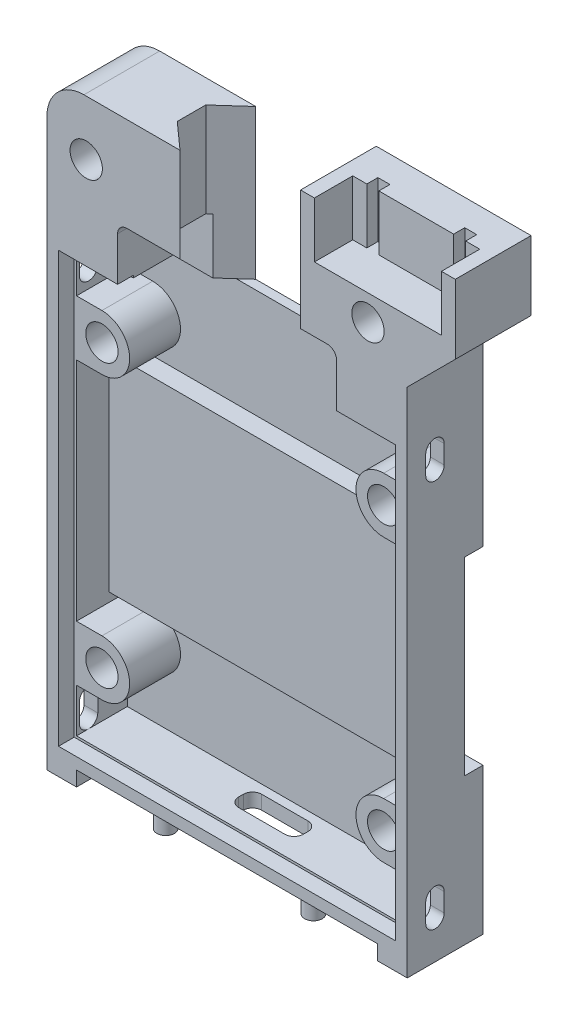
SolidWorks part; units mm, degrees
ref_plane "Front Plane" through (0, 0, 0) normal (0, 0, 1) x (1, 0, 0)
ref_plane "Top Plane" through (0, 0, 0) normal (0, 1, 0) x (1, 0, 0)
ref_plane "Right Plane" through (0, 0, 0) normal (1, 0, 0) x (0, 0, -1)
sketch "Sketch1" plane through (0, 0, 0) normal (0, 0, 1) x (1, 0, 0)
  line L0 (15.25, -20.35) -> (18, -20.35)
  line L1 (-19.5, -32.6) -> (19.5, -32.6)
  line L2 (-19.5, -32.6) -> (-19.5, 31.1)
  line L3 (-19.5, 31.1) -> (19.5, 31.1)
  line L4 (19.5, -32.6) -> (19.5, 31.1)
  line L5 (-15.25, -20.35) -> (-18, -20.35)
  line L6 (15.25, -26.35) -> (18, -26.35)
  line L7 (6.95, 31.1) -> (-15.5, 31.1) construction
  line L8 (-18, -31.1) -> (-18, 29.6)
  line L9 (-18, 29.6) -> (18, 29.6)
  line L10 (18, -31.1) -> (18, 29.6)
  line L11 (-18, -31.1) -> (18, -31.1)
  line L12 (-18, 14.9) -> (18, 14.9)
  line L13 (7.85, 14.9) -> (-4.95, 14.9) construction
  line L14 (-15.25, 4.15) -> (-18, 4.15)
  line L15 (-15.25, 10.15) -> (-18, 10.15)
  line L16 (15.25, 10.15) -> (18, 10.15)
  line L17 (15.25, 4.15) -> (18, 4.15)
  line L18 (-15.25, -26.35) -> (-18, -26.35)
  line L19 (19.5, -34.2) -> (19.5, -18.35) construction
  line L20 (-19.5, -34.2) -> (-19.5, -18.35) construction
  line L21 (15.3, -32.6) -> (-15.3, -32.6) construction
  line L22 (0, 31.1) -> (0, -32.6) construction
  line L23 (9.45, 26.9) -> (24.7, 26.9)
  line L24 (9.45, 26.9) -> (9.45, 33.9)
  line L25 (9.45, 33.9) -> (24.7, 33.9)
  line L26 (24.7, 26.9) -> (24.7, 33.9)
  line L27 (18, 29.6) -> (19.5, 31.1) construction
  line L28 (18.75, 30.35) -> (0, 30.35) construction
  line L29 (9.45, 26.9) -> (7.95, 26.9) construction
  line L30 (-7.95, 31.1) -> (7.95, 31.1)
  line L31 (-7.95, 31.1) -> (-7.95, 29.6)
  line L32 (-7.95, 29.6) -> (7.95, 29.6)
  line L33 (7.95, 31.1) -> (7.95, 29.6)
  line L34 (-7.95, 31.1) -> (7.95, 29.6) construction
  line L35 (-7.95, 29.6) -> (7.95, 31.1) construction
  line L36 (7.95, 26.9) -> (7.95, 29.6) construction
  line L37 (18, 29.6) -> (19.5, 29.6) construction
  line L38 (24.7, 26.4) -> (19.5, 21.2)
  line L39 (9.45, 33.9) -> (7.95, 33.9)
  line L40 (23.2, 33.9) -> (23.2, 26.9)
  line L41 (7.95, 33.9) -> (7.95, 31.1)
  line L42 (24.7, 30.4) -> (23.2, 30.4) construction
  line L43 (24.7, 26.9) -> (19.5, 26.9)
  line L44 (24.7, 26.9) -> (24.7, 26.4)
  line L45 (24.7, 26.4) -> (19.5, 26.4)
  line L46 (19.5, 26.9) -> (19.5, 26.4)
  circle A0 centre (15.25, -23.35) radius 1.75
  arc A1 (-15.5, 31.1) -> (-19.5, 27.1) centre (-15.5, 27.1) ccw construction
  circle A2 centre (15.25, -23.35) radius 3
  arc A3 (-15.5, 31.1) -> (-19.5, 27.1) centre (-15.5, 27.1) ccw
  arc A4 (-15.5, 29.6) -> (-18, 27.1) centre (-15.5, 27.1) ccw
  circle A6 centre (-15.25, -23.35) radius 1.75
  circle A7 centre (-15.25, -23.35) radius 1.75
  circle A8 centre (-15.25, 7.15) radius 1.75
  circle A9 centre (15.25, 7.15) radius 1.75
  circle A10 centre (15.25, 25.15) radius 1.75
  circle A11 centre (-15.25, 25.15) radius 1.75
  circle A12 centre (-15.25, -23.35) radius 3
  circle A13 centre (-15.25, -23.35) radius 3
  circle A14 centre (15.25, 7.15) radius 3
  circle A15 centre (-15.25, 7.15) radius 3
  dimension "D2" = 1.5
  dimension "D4" = 6
  dimension "D3" = 3.5
  dimension "D5" = 13.75
  dimension "D6" = 15.9
  dimension "D7" = 7
  dimension "D8" = 45
  dimension "D9" = 0.5
  dimension "D1" = 1.5
extrude "Base shape" add sketch "Sketch1" along normal up to surface (8.2 mm away) contours A15 L8 L9 L31 L3 A3 L2 L1 L4 L23 L10 A14 A2 L11 A12 | A12 L8 L18 | A12 L8 A6 | L8 A12 | A12 L5 L8 | A15 L8 L14 | A15 L8 A8 | L8 A15 | A15 L15 L8 | L23 A10 L24 L9 A4 L8 L12 L10 A11 | A4 L9 L8 | L33 L3 L31 L9 | L3 L33 L9 L24 | L24 L9 L10 L23 L4 L3 | L24 L23 L10 L9 | A14 L10 L16 | L10 A14 A9 | A14 L17 L10 | L10 A14 | L10 A2 L6 | A2 L10 A0 | L0 A2 L10 | A2 L10 | L40 L25 L24 L3 L4 L23 | L25 L40 L23 L26 | L38 L45 L4 | L45 L44 L23 L4 | L39 L41 L3 L24 region at (16.8481, -20.9099, 0) region at (17.3601, -20.8437, 0) region at (18.7469, -8.1, 0) region at (17.3601, -25.8563, 0) region at (18.1004, -23.35, 0) region at (17.3601, 4.6437, 0) region at (16.8481, 4.7099, 0) region at (18.1004, 7.15, 0) region at (17.3601, 9.6563, 0) region at (-17.3601, -25.8563, 0) region at (-0.6044, 21.831, 0) region at (-18.1004, -23.35, 0) region at (-17.9169, -23.35, 0) region at (13.725, 28.25, 0) region at (15.3803, 29.9053, 0) region at (-17.3601, -20.8437, 0) region at (22.1, 26.65, 0) region at (17.77, 31.4935, 0) region at (-17.3601, 9.6563, 0) region at (-17.4416, 29.0416, 0) region at (8.7, 30.35, 0) region at (21.2333, 24.6667, 0) region at (23.95, 30.4, 0) region at (-16.8481, 9.5901, 0) region at (-18.1004, 7.15, 0) region at (-17.3601, 4.6437, 0) region at (0, 30.35, 0) region at (8.7, 32.5, 0)
sketch "Sketch3" plane through (19.5, 0, 0) normal (1, 0, 0) x (0, 0, -1)
  line L1 (0, -18.35) -> (-2, -18.35)
  line L2 (0, -18.35) -> (0, 2.15)
  line L3 (0, 2.15) -> (-2, 2.15)
  line L4 (-2, -18.35) -> (-2, 2.15)
  line L5 (0, -18.35) -> (1.75, -18.35) construction
  line L6 (0, 2.15) -> (1.75, 2.15) construction
  line L7 (0, -32.6) -> (0, 21.2) construction
  dimension "D1" = 2
extrude "Strap cut" cut sketch "Sketch3" against normal through all
sketch "Sketch4" plane through (0, 31.1, 0) normal (0, 1, 0) x (1, 0, 0)
  line L2 (7.95, 0) -> (-5.0998, 0)
  line L4 (-15.5, 0) -> (7.95, 0) construction
  line L5 (-15.5, -8.2) -> (7.95, -8.2) construction
  line L6 (7.95, -8.2) -> (-5.0998, -8.2)
  line L12 (7.95, -8.3) -> (7.95, 0.1)
  line L13 (7.95, 0.1) -> (-4.9883, 0.1)
  line L14 (-4.9883, 0.1) -> (-7.95, -2.5553)
  line L15 (-7.95, -2.5553) -> (-7.95, -5.6447)
  line L16 (-7.95, -5.6447) -> (-4.9883, -8.3)
  line L17 (-4.9883, -8.3) -> (7.95, -8.3)
  line L18 (7.95, -8.3) -> (7.95, 0.1)
  line L19 (7.95, 0.1) -> (-4.9883, 0.1)
  line L20 (-4.9883, 0.1) -> (-7.95, -2.5553)
  line L21 (-7.95, -2.5553) -> (-7.95, -5.6447)
  line L22 (-7.95, -5.6447) -> (-4.9883, -8.3)
  line L23 (-4.9883, -8.3) -> (7.95, -8.3)
  dimension "D1" = 0.1
extrude "XT60 cut" cut sketch "Sketch4" against normal up to next contours L21 L22 L18 L20 region at (0.4142, 31.1, 4.1)
sketch "Sketch5" plane through (19.5, 0, 0) normal (1, 0, 0) x (0, 0, -1)
  line L1 (-8.2, -32.6) -> (-8.2, 21.2) construction
  line L2 (-6.2, -31.1) -> (-4.2, -31.1)
  line L3 (-6.2, -31.1) -> (-6.2, -27.1)
  line L4 (-6.2, -27.1) -> (-4.2, -27.1)
  line L5 (-4.2, -31.1) -> (-4.2, -27.1)
  line L6 (-8.2, -31.1) -> (0, -31.1) construction
  line L7 (-8.2, 14.9) -> (0, 14.9) construction
  line L8 (-6.2, 14.9) -> (-4.2, 14.9)
  line L9 (-6.2, 14.9) -> (-6.2, 10.9)
  line L10 (-6.2, 10.9) -> (-4.2, 10.9)
  line L11 (-4.2, 14.9) -> (-4.2, 10.9)
  line L14 (-5.2, -27.1) -> (-5.2, -31.1) construction
  line L15 (-5.2, 14.9) -> (-5.2, 10.9) construction
  circle A0 centre (-5.2, -28.1) radius 1
  circle A1 centre (-5.2, -30.1) radius 1
  circle A2 centre (-5.2, 13.9) radius 1
  circle A3 centre (-5.2, 11.9) radius 1
  point P20 (-5.2, -29.1)
  point P31 (-5.2, 12.9)
  dimension "D3" = 4
  dimension "D1" = 2
  dimension "D2" = 2
extrude "Power wires cut" cut sketch "Sketch5" against normal through all contours A2 | A3 | A3 A2 L9 | A3 L11 A2 | A1 | A0 | A1 L5 A0 | A1 A0 L3 region at (19.5, -30.1, 5.2) region at (19.5, -29.1, 5.9766) region at (19.5, -29.1, 4.4234) region at (19.5, -28.1, 5.2) region at (19.5, 13.9, 5.2) region at (19.5, 12.9, 5.9766) region at (19.5, 12.9, 4.4234) region at (19.5, 11.9, 5.2)
sketch "Sketch6" plane through (0, 0, 8.2) normal (0, 0, 1) x (1, 0, 0)
  line L5 (-10.85, 20.9) -> (10.85, 20.9)
  line L6 (10.85, 14.9) -> (8.85, 14.9) construction
  line L7 (-11.85, 19.9) -> (11.85, 19.9)
  line L12 (-11.85, 19.9) -> (-11.85, 14.9)
  line L14 (-11.85, 14.9) -> (11.85, 14.9)
  line L15 (11.85, 19.9) -> (11.85, 14.9)
  arc A7 (11.85, 19.9) -> (10.85, 20.9) centre (10.85, 19.9) ccw construction
  arc A12 (11.85, 19.9) -> (10.85, 20.9) centre (10.85, 19.9) ccw
  arc A13 (-10.85, 20.9) -> (-11.85, 19.9) centre (-10.85, 19.9) ccw construction
  arc A14 (-10.85, 20.9) -> (-11.85, 19.9) centre (-10.85, 19.9) ccw
  point P9 (0, 0)
extrude "IO wires cut" cut sketch "Sketch6" against normal blind 6
sketch "Sketch7" plane through (-18, 0, 0) normal (1, 0, 0) x (0, 0, -1)
  line L6 (0, -18.35) -> (0, -20.35)
  line L7 (-2, -18.35) -> (0, -18.35)
  line L8 (-2, 2.15) -> (-2, -18.35)
  line L9 (0, 2.15) -> (-2, 2.15)
  line L12 (0, 3.15) -> (-3, 3.15)
  line L13 (-3, 3.15) -> (-3, -19.35)
  line L14 (-3, -19.35) -> (-1, -19.35)
  line L15 (-1, -19.35) -> (-1, -20.35)
  line L16 (-1, -20.35) -> (0, -20.35)
  line L17 (0, 3.15) -> (-1, 3.15)
  line L19 (0, -31.1) -> (-1, -31.1)
  line L22 (0, -31.1) -> (0, -20.35)
  line L23 (0, -20.35) -> (-1, -20.35)
  line L24 (-1, -31.1) -> (-1, -20.35)
  line L25 (0, 3.15) -> (0, 14.9)
  line L26 (0, 14.9) -> (-1, 14.9)
  line L27 (-1, 3.15) -> (-1, 14.9)
  line L28 (-5.2, 14.9) -> (0, 14.9) construction
  line L31 (0, -20.35) -> (0, -18.35) construction
  line L32 (0, 2.15) -> (-2, 2.15) construction
  line M48 (0, -20.35) -> (0, -18.35)
  line M49 (0, -18.35) -> (-2, -18.35)
  line M50 (-2, -18.35) -> (-2, 2.15)
  line M51 (-2, 2.15) -> (0, 2.15)
  line M52 (0, 2.15) -> (0, 4.15)
  line M53 (0, 4.15) -> (-8.2, 4.15)
  line M55 (-8.2, -20.35) -> (0, -20.35)
  dimension "D1" = 1
extrude "Bottom" add sketch "Sketch7" along normal up to surface (36 mm away) contours L27 L25 L26 M53 | L27 L12 M52 M53 | L14 L15 L12 L13 M55 M48 M49 M50 M51 M52 | L24 L19 L22 M55 region at (-18, -8.5273, 2.2091) region at (-18, -25.725, 0.5) region at (-18, 3.65, 0.5) region at (-18, 9.525, 0.5) up to face at (18, -8.1, 2.55)
sketch "Sketch9" plane through (0, 0, 0) normal (0, 0, -1) x (-1, 0, 0)
  circle A0 centre (15.25, -23.35) radius 1.75 construction
  circle A1 centre (-15.25, 7.15) radius 1.75 construction
  circle A2 centre (15.25, 7.15) radius 1.75 construction
  circle A3 centre (15.25, -23.35) radius 1.75 construction
  circle A4 centre (15.25, -23.35) radius 1.75
  circle A5 centre (-15.25, 7.15) radius 1.75
  circle A6 centre (15.25, 7.15) radius 1.75
  circle A7 centre (15.25, -23.35) radius 1.75
  circle A8 centre (-15.25, -23.35) radius 1.75 construction
  circle A9 centre (-15.25, -23.35) radius 1.75
extrude "Bottom holes" cut sketch "Sketch9" against normal up to next contours A5 | A6 | A4 | A9 region at (-15.25, -23.35, 0) region at (15.25, 7.15, 0) region at (-15.25, 7.15, 0) region at (15.25, -23.35, 0)
sketch "Sketch8" plane through (0, 0, 8.2) normal (0, 0, 1) x (1, 0, 0)
  line L0 (-6.2152, 14.9) -> (-18, 14.9) construction
  line L1 (-18.25, 15.15) -> (18.25, 15.15)
  line L2 (-18.25, 15.15) -> (-18.25, -31.35)
  line L3 (-18.25, -31.35) -> (18.25, -31.35)
  line L4 (18.25, 15.15) -> (18.25, -31.35)
  line L5 (-18, 14.9) -> (-18.25, 14.9) construction
  line L6 (-18, 14.9) -> (-18, 15.15) construction
  line L7 (18, 14.9) -> (18.25, 14.9) construction
  line L8 (-18, -31.1) -> (-18, -31.35) construction
  dimension "D1" = 0.25
extrude "PCB cut" cut sketch "Sketch8" against normal blind 1.7
sketch "Sketch11" plane through (0, -32.6, 0) normal (0, -1, 0) x (1, 0, 0)
  line L0 (19.5, 8.2) -> (19.5, 0) construction
  line L1 (-19.5, 8.2) -> (19.5, 8.2)
  line L2 (-19.5, 8.2) -> (-19.5, -1.8)
  line L3 (-19.5, -1.8) -> (19.5, -1.8)
  line L4 (19.5, 8.2) -> (19.5, -1.8)
  line L5 (-19.5, 3.2) -> (19.5, 3.2) construction
  line L6 (0, -1.8) -> (0, 8.2) construction
  line L8 (-2.5, 4.45) -> (2.5, 4.45)
  line L9 (-3.5, 3.45) -> (-3.5, 2.95)
  line L10 (-2.5, 1.95) -> (2.5, 1.95)
  line L11 (3.5, 3.45) -> (3.5, 2.95)
  line L12 (-3.5, 4.45) -> (3.5, 1.95) construction
  line L13 (-3.5, 1.95) -> (3.5, 4.45) construction
  arc A0 (2.5, 4.45) -> (3.5, 3.45) centre (2.5, 3.45) cw
  arc A1 (2.5, 1.95) -> (3.5, 2.95) centre (2.5, 2.95) ccw
  arc A2 (-3.5, 2.95) -> (-2.5, 1.95) centre (-2.5, 2.95) ccw
  arc A3 (-2.5, 4.45) -> (-3.5, 3.45) centre (-2.5, 3.45) ccw
  point P11 (0, 3.2)
  dimension "D4" = 1
  dimension "D1" = 10
  dimension "D2" = 7
  dimension "D3" = 2.5
extrude "Ledbar wires cut" cut sketch "Sketch11" against normal up to next contours L8 A3 L9 A2 L10 A1 L11 A0 region at (0, -32.6, 3.2)
sketch "Sketch13" plane through (0, -32.6, 0) normal (0, -1, 0) x (1, 0, 0)
  line L0 (-19.5, 8.2) -> (19.5, 8.2) construction
  line L1 (19.5, 0) -> (16.3, 0)
  line L2 (19.5, 0) -> (19.5, 8.2)
  line L3 (19.5, 8.2) -> (16.3, 8.2)
  line L4 (16.3, 0) -> (16.3, 8.2)
  line L5 (16.1, -1.8) -> (16.1, 8.2) construction
  line L6 (0, 8.2) -> (0, 0) construction
  line L7 (-19.5, 0) -> (-16.3, 0)
  line L8 (-19.5, 0) -> (-19.5, 8.2)
  line L9 (-19.5, 8.2) -> (-16.3, 8.2)
  line L10 (-16.3, 0) -> (-16.3, 8.2)
  dimension "D1" = 0.2
extrude "Ledbar sides" add sketch "Sketch13" along normal blind 1.6
sketch "Sketch14" plane through (0, -32.6, 0) normal (0, -1, 0) x (1, 0, 0)
  circle A0 centre (8, 6.85) radius 0.95
  circle A1 centre (-8, 6.85) radius 0.95
  dimension "D1" = 1.9
extrude "Ledbar mounts" add sketch "Sketch14" along normal blind 2
sketch "Sketch16" plane through (0, 33.9, 0) normal (0, 1, 0) x (1, 0, 0)
  line L0 (7.95, -6.125) -> (24.7, -6.125) construction
  line L1 (7.95, -8.2) -> (24.7, -8.2) construction
  line L2 (21.675, -2.85) -> (20.375, -2.85)
  line L3 (20.375, -4.05) -> (20.375, -2.85)
  line L4 (9.45, -4.05) -> (23.2, -4.05)
  line L5 (9.45, -4.05) -> (9.45, -8.2)
  line L6 (9.45, -8.2) -> (23.2, -8.2)
  line L7 (23.2, -4.05) -> (23.2, -8.2)
  line L8 (9.45, -4.05) -> (23.2, -8.2) construction
  line L9 (9.45, -8.2) -> (23.2, -4.05) construction
  line L10 (24.7, -8.2) -> (24.7, 0) construction
  line L11 (7.95, -8.2) -> (7.95, 0) construction
  line L12 (16.325, -8.2) -> (16.325, -4.05) construction
  line L13 (11.625, -2.85) -> (11.625, -4.05) construction
  line L14 (10.975, -4.05) -> (12.275, -4.05)
  line L15 (10.975, -4.05) -> (10.975, -2.85)
  line L16 (10.975, -2.85) -> (12.275, -2.85)
  line L17 (12.275, -4.05) -> (12.275, -2.85)
  line L18 (10.975, -2.85) -> (10.975, -8.2) construction
  line L19 (21.675, -4.05) -> (21.675, -2.85)
  point P6 (16.325, -6.125)
  dimension "D1" = 13.75
  dimension "D2" = 4.15
  dimension "D3" = 1.3
  dimension "D4" = 1.2
  dimension "D5" = 4.7
extrude "Balance plug cut" cut sketch "Sketch16" against normal blind 6 contours L7 L4 L5 L6 | L4 L17 L16 L15 | L4 L19 L2 L3 region at (21.025, 33.9, 3.45) region at (16.325, 33.9, 6.125) region at (11.625, 33.9, 3.45)
sketch "Sketch10" [suppressed] plane through (0, 0, 2) normal (0, 0, -1) x (-1, 0, 0)
  line L0 (0, 2.15) -> (0, -18.35) construction
  line L1 (19.5, 2.15) -> (-19.5, 2.15) construction
  line L2 (19.5, -18.35) -> (-19.5, -18.35) construction
  line L3 (19.5, 2.15) -> (19.5, -18.35) construction
  line L4 (-19.5, 1.15) -> (19.5, 1.15)
  line L5 (-19.5, 1.15) -> (-19.5, 0.65)
  line L6 (-19.5, 0.65) -> (19.5, 0.65)
  line L7 (19.5, 1.15) -> (19.5, 0.65)
  line L8 (-19.5, 1.15) -> (19.5, 0.65) construction
  line L9 (-19.5, 0.65) -> (19.5, 1.15) construction
  line L10 (-19.5, 2.15) -> (19.5, 2.15) construction
  line L11 (-19.5, -1.35) -> (19.5, -1.35)
  line L12 (19.5, -0.85) -> (19.5, -1.35)
  line L13 (-19.5, -0.85) -> (19.5, -0.85)
  line L14 (-19.5, -0.85) -> (-19.5, -1.35)
  line L15 (-19.5, -3.35) -> (19.5, -3.35)
  line L16 (19.5, -2.85) -> (19.5, -3.35)
  line L17 (-19.5, -2.85) -> (19.5, -2.85)
  line L18 (-19.5, -2.85) -> (-19.5, -3.35)
  line L19 (-19.5, -5.35) -> (19.5, -5.35)
  line L20 (19.5, -4.85) -> (19.5, -5.35)
  line L21 (-19.5, -4.85) -> (19.5, -4.85)
  line L22 (-19.5, -4.85) -> (-19.5, -5.35)
  line L23 (-19.5, -7.35) -> (19.5, -7.35)
  line L24 (19.5, -6.85) -> (19.5, -7.35)
  line L25 (-19.5, -6.85) -> (19.5, -6.85)
  line L26 (-19.5, -6.85) -> (-19.5, -7.35)
  line L27 (-19.5, -9.35) -> (19.5, -9.35)
  line L28 (19.5, -8.85) -> (19.5, -9.35)
  line L29 (-19.5, -8.85) -> (19.5, -8.85)
  line L30 (-19.5, -8.85) -> (-19.5, -9.35)
  line L31 (-19.5, -11.35) -> (19.5, -11.35)
  line L32 (19.5, -10.85) -> (19.5, -11.35)
  line L33 (-19.5, -10.85) -> (19.5, -10.85)
  line L34 (-19.5, -10.85) -> (-19.5, -11.35)
  line L35 (-19.5, -13.35) -> (19.5, -13.35)
  line L36 (19.5, -12.85) -> (19.5, -13.35)
  line L37 (-19.5, -12.85) -> (19.5, -12.85)
  line L38 (-19.5, -12.85) -> (-19.5, -13.35)
  line L39 (-19.5, -15.35) -> (19.5, -15.35)
  line L40 (19.5, -14.85) -> (19.5, -15.35)
  line L41 (-19.5, -14.85) -> (19.5, -14.85)
  line L42 (-19.5, -14.85) -> (-19.5, -15.35)
  line L43 (-19.5, -17.35) -> (19.5, -17.35)
  line L44 (19.5, -16.85) -> (19.5, -17.35)
  line L45 (-19.5, -16.85) -> (19.5, -16.85)
  line L46 (-19.5, -16.85) -> (-19.5, -17.35)
  point P6 (0, 0.9)
  dimension "D1" = 1
  dimension "D2" = 0.5
  dimension "D4" = 2
  dimension "D3" = 10
extrude "3D print ribs" [suppressed] add sketch "Sketch10" along normal up to surface (2 mm away) up to face at (-17, 7.15, 0)
sketch "Sketch15" [suppressed] plane through (0, 0, 0) normal (0, 0, -1) x (-1, 0, 0)
  line L0 (-8, -34.6) -> (-8, -32.6) construction
  line L1 (-8.95, -34.6) -> (-7.05, -34.6) construction
  line L2 (-8.95, -32.6) -> (-7.05, -32.6) construction
  line L3 (0, -32.6) -> (0, 14.9) construction
  line L4 (-8.25, -34.6) -> (-7.75, -34.6)
  line L5 (-8.25, -34.6) -> (-8.25, -32.6)
  line L6 (-8.25, -32.6) -> (-7.75, -32.6)
  line L7 (-7.75, -34.6) -> (-7.75, -32.6)
  line L8 (-8.25, -34.6) -> (-7.75, -32.6) construction
  line L9 (-8.25, -32.6) -> (-7.75, -34.6) construction
  line L10 (16.3, -32.6) -> (-16.3, -32.6) construction
  line L11 (-7.95, 14.9) -> (5.0998, 14.9) construction
  line L12 (8.25, -32.6) -> (7.75, -32.6)
  line L13 (7.75, -34.6) -> (7.75, -32.6)
  line L14 (8.25, -34.6) -> (7.75, -34.6)
  line L15 (8.25, -34.6) -> (8.25, -32.6)
  point P6 (-8, -33.6)
  dimension "D1" = 0.5
extrude "3D print led supports" [suppressed] add sketch "Sketch15" against normal up to next
